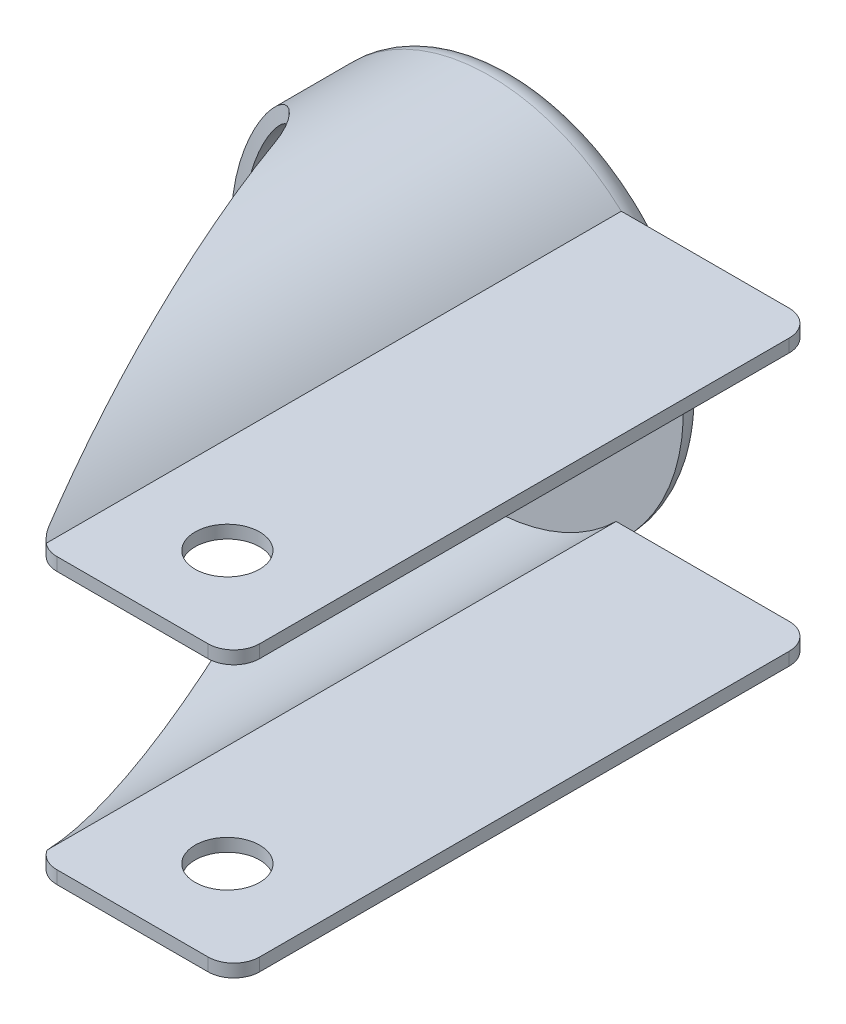
SolidWorks part; units mm, degrees
ref_plane "前视基准面" through (0, 0, 0) normal (0, 0, 1) x (1, 0, 0)
ref_plane "上视基准面" through (0, 0, 0) normal (0, 1, 0) x (1, 0, 0)
ref_plane "右视基准面" through (0, 0, 0) normal (1, 0, 0) x (0, 0, -1)
sketch "草图1" plane through (0, 0, 0) normal (0, 0, 1) x (1, 0, 0)
  line L0 (0, 0) -> (15, 0) construction
  line L2 (10.198, -11) -> (25.198, -11)
  line L4 (10.198, 11) -> (25.198, 11)
  line L5 (25.198, -11) -> (25.198, 11)
  arc A0 (10.198, 11) -> (10.198, -11) centre (0, 0) ccw
  dimension "D1" = 30
  dimension "D2" = 22
  dimension "D3" = 15
  dimension "D4" = 11
extrude "凸台-拉伸1" add sketch "草图1" along normal blind 45
shell "抽壳11" thickness 1 removed face at (25.198, 0, 22.5) removed face at (11.3985, 0, 45) removed face at (11.3985, 0, 0)
sketch "草图2" plane through (0, 0, 0) normal (0, 1, 0) x (1, 0, 0)
  line L0 (-15, 0) -> (-15, -5) construction
  line L1 (-15, 0) -> (-15, -45) construction
  line L2 (10.198, -45) -> (-4.5262, -12.0897)
  line L3 (-15, -5) -> (-15, -45)
  line L4 (-15, -45) -> (10.198, -45)
  arc A0 (-4.5262, -12.0897) -> (-15, -5) centre (-15.4798, -16.9904) ccw
  dimension "D2" = 12
  dimension "D1" = 5
  dimension "D3" = 32.9103
extrude "切除-拉伸3" cut sketch "草图2" against normal through all both and the other way through all
sketch "草图3" plane through (0, 11, 0) normal (0, 1, 0) x (1, 0, 0)
  line L0 (17.698, -45) -> (17.698, -38) construction
  line L1 (25.198, -45) -> (10.198, -45) construction
  circle A0 centre (17.698, -38) radius 2.5
  dimension "D2" = 5
  dimension "D1" = 7
extrude "切除-拉伸5" cut sketch "草图3" against normal through all both and the other way through all
sketch "草图5" plane through (0, 0, 0) normal (0, 0, -1) x (-1, 0, 0)
  circle A0 centre (0, 0) radius 15
  dimension "D1" = 30
extrude "凸台-拉伸4" add sketch "草图5" along normal blind 2
fillet "圆角5" radius 2 1 edges at (-15, 0, -2)
sketch "草图6" plane through (0, 0, -2) normal (0, 0, -1) x (-1, 0, 0)
  circle A0 centre (0, 0) radius 5
  dimension "D1" = 10
extrude "切除-拉伸6" cut sketch "草图6" against normal through all both and the other way through all
fillet "圆角6" radius 2 2 edges at (25.198, 10.5, 0) (25.198, 10.5, 45)
fillet "圆角7" radius 2 4 edges at (10.198, -10.5, 45) (10.198, 10.5, 45) (25.198, -10.5, 0) (25.198, -10.5, 45)
